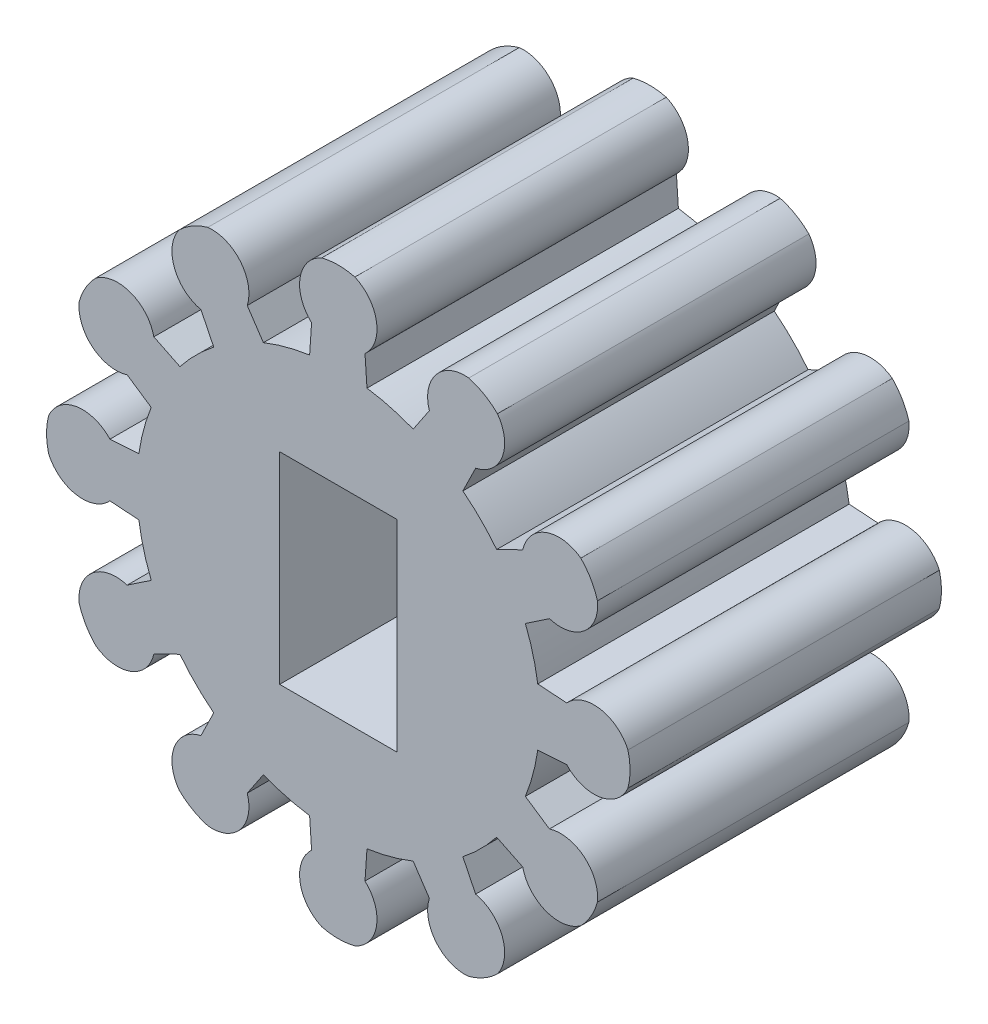
SolidWorks part; units mm, degrees
ref_plane "Front Plane" through (0, 0, 0) normal (0, 0, 1) x (1, 0, 0)
ref_plane "Top Plane" through (0, 0, 0) normal (0, 1, 0) x (1, 0, 0)
ref_plane "Right Plane" through (0, 0, 0) normal (1, 0, 0) x (0, 0, -1)
ref_plane "Plane1" through (0, 0, 20) normal (0, 0, 1) x (1, 0, 0)
ref_plane "Plane2" through (0, 0, 28.5) normal (0, 0, 1) x (1, 0, 0)
sketch "Sketch1" plane through (0, 0, 20) normal (0, 0, 1) x (1, 0, 0)
  circle A1 centre (0, 20.9252) radius 5.5
  dimension "D1" = 11
sketch "Sketch3" plane through (0, 0, 28.5) normal (0, 0, 1) x (1, 0, 0)
  line L0 (-3.9726, 20.9252) -> (15.3734, 20.9252) construction
  line L1 (0, 24.8978) -> (0, 8.7425) construction
  line L3 (-1.6, 23.6752) -> (1.6, 23.6752)
  line L4 (-1.6, 23.6752) -> (-1.6, 18.1752)
  line L5 (-1.6, 18.1752) -> (1.6, 18.1752)
  line L6 (1.6, 23.6752) -> (1.6, 18.1752)
  dimension "D1" = 3.2
  dimension "D2" = 5.5
  dimension "D3" = 1.6
  dimension "D4" = 2.75
extrude "Boss-Extrude2" add sketch "Sketch1" along normal blind 8.5
extrude "Cut-Extrude1" cut sketch "Sketch3" against normal blind 6
sketch "Sketch4" plane through (0, 0, 20) normal (0, 0, 1) x (1, 0, 0)
  line L0 (-0.729, 27.1591) -> (-0.7828, 26.3692)
  line L1 (0, 28.8881) -> (0, 27.9031) construction
  line L2 (0.729, 27.1591) -> (0.7828, 26.3692)
  line L3 (3.7483, 25.9594) -> (3.4, 25.2485)
  line L4 (2.4856, 26.6885) -> (2.044, 26.0313)
  line L5 (5.7632, 23.4108) -> (5.1061, 22.9693)
  line L6 (5.0342, 24.6735) -> (4.3232, 24.3252)
  line L7 (6.2339, 20.1962) -> (5.444, 20.1424)
  line L8 (6.2339, 21.6542) -> (5.444, 21.7081)
  line L9 (5.0342, 17.177) -> (4.3232, 17.5253)
  line L10 (5.7632, 18.4396) -> (5.1061, 18.8812)
  line L11 (2.4856, 15.162) -> (2.044, 15.8192)
  line L12 (3.7483, 15.891) -> (3.4, 16.602)
  line L13 (-0.729, 14.6913) -> (-0.7828, 15.4812)
  line L14 (0.729, 14.6913) -> (0.7828, 15.4812)
  line L15 (-3.7483, 15.891) -> (-3.4, 16.602)
  line L16 (-2.4856, 15.162) -> (-2.044, 15.8192)
  line L17 (-5.7632, 18.4396) -> (-5.1061, 18.8812)
  line L18 (-5.0342, 17.177) -> (-4.3232, 17.5253)
  line L19 (-6.2339, 21.6542) -> (-5.444, 21.7081)
  line L20 (-6.2339, 20.1962) -> (-5.444, 20.1424)
  line L21 (-5.0342, 24.6735) -> (-4.3232, 24.3252)
  line L22 (-5.7632, 23.4108) -> (-5.1061, 22.9693)
  line L23 (-2.4856, 26.6885) -> (-2.044, 26.0313)
  line L24 (-3.7483, 25.9594) -> (-3.4, 25.2485)
  circle A0 centre (0, 20.9252) radius 5.5 construction
  arc A1 (-0.729, 27.1591) -> (-0.4523, 28.8311) centre (-0.0445, 27.9047) cw
  arc A2 (-0.4523, 28.8311) -> (0.4523, 28.8311) centre (0, 27.0672) cw
  arc A3 (0.729, 27.1591) -> (0.4523, 28.8311) centre (0.0445, 27.9047) ccw
  arc A4 (-0.7828, 26.3692) -> (0.7828, 26.3692) centre (0, 20.9252) cw
  arc A5 (2.044, 26.0313) -> (3.4, 25.2485) centre (0, 20.9252) cw
  arc A6 (3.7483, 25.9594) -> (4.3446, 27.5457) centre (3.5283, 26.9474) ccw
  arc A7 (3.5612, 27.998) -> (4.3446, 27.5457) centre (3.071, 26.2443) cw
  arc A8 (2.4856, 26.6885) -> (3.5612, 27.998) centre (3.4512, 26.9919) cw
  arc A9 (4.3232, 24.3252) -> (5.1061, 22.9693) centre (0, 20.9252) cw
  arc A10 (5.7632, 23.4108) -> (7.0728, 24.4865) centre (6.0667, 24.3764) ccw
  arc A11 (6.6205, 25.2699) -> (7.0728, 24.4865) centre (5.3191, 23.9962) cw
  arc A12 (5.0342, 24.6735) -> (6.6205, 25.2699) centre (6.0221, 24.4535) cw
  arc A13 (5.444, 21.7081) -> (5.444, 20.1424) centre (0, 20.9252) cw
  arc A14 (6.2339, 20.1962) -> (7.9058, 20.4729) centre (6.9795, 20.8807) ccw
  arc A15 (7.9058, 21.3775) -> (7.9058, 20.4729) centre (6.1419, 20.9252) cw
  arc A16 (6.2339, 21.6542) -> (7.9058, 21.3775) centre (6.9795, 20.9698) cw
  arc A17 (5.1061, 18.8812) -> (4.3232, 17.5253) centre (0, 20.9252) cw
  arc A18 (5.0342, 17.177) -> (6.6205, 16.5806) centre (6.0221, 17.3969) ccw
  arc A19 (7.0728, 17.364) -> (6.6205, 16.5806) centre (5.3191, 17.8543) cw
  arc A20 (5.7632, 18.4396) -> (7.0728, 17.364) centre (6.0667, 17.4741) cw
  arc A21 (3.4, 16.602) -> (2.044, 15.8192) centre (0, 20.9252) cw
  arc A22 (2.4856, 15.162) -> (3.5612, 13.8524) centre (3.4512, 14.8586) ccw
  arc A23 (4.3446, 14.3047) -> (3.5612, 13.8524) centre (3.071, 15.6062) cw
  arc A24 (3.7483, 15.891) -> (4.3446, 14.3047) centre (3.5283, 14.9031) cw
  arc A25 (0.7828, 15.4812) -> (-0.7828, 15.4812) centre (0, 20.9252) cw
  arc A26 (-0.729, 14.6913) -> (-0.4523, 13.0194) centre (-0.0445, 13.9458) ccw
  arc A27 (0.4523, 13.0194) -> (-0.4523, 13.0194) centre (0, 14.7833) cw
  arc A28 (0.729, 14.6913) -> (0.4523, 13.0194) centre (0.0445, 13.9458) cw
  arc A29 (-2.044, 15.8192) -> (-3.4, 16.602) centre (0, 20.9252) cw
  arc A30 (-3.7483, 15.891) -> (-4.3446, 14.3047) centre (-3.5283, 14.9031) ccw
  arc A31 (-3.5612, 13.8524) -> (-4.3446, 14.3047) centre (-3.071, 15.6062) cw
  arc A32 (-2.4856, 15.162) -> (-3.5612, 13.8524) centre (-3.4512, 14.8586) cw
  arc A33 (-4.3232, 17.5253) -> (-5.1061, 18.8812) centre (0, 20.9252) cw
  arc A34 (-5.7632, 18.4396) -> (-7.0728, 17.364) centre (-6.0667, 17.4741) ccw
  arc A35 (-6.6205, 16.5806) -> (-7.0728, 17.364) centre (-5.3191, 17.8543) cw
  arc A36 (-5.0342, 17.177) -> (-6.6205, 16.5806) centre (-6.0221, 17.3969) cw
  arc A37 (-5.444, 20.1424) -> (-5.444, 21.7081) centre (0, 20.9252) cw
  arc A38 (-6.2339, 21.6542) -> (-7.9058, 21.3775) centre (-6.9795, 20.9698) ccw
  arc A39 (-7.9058, 20.4729) -> (-7.9058, 21.3775) centre (-6.1419, 20.9252) cw
  arc A40 (-6.2339, 20.1962) -> (-7.9058, 20.4729) centre (-6.9795, 20.8807) cw
  arc A41 (-5.1061, 22.9693) -> (-4.3232, 24.3252) centre (0, 20.9252) cw
  arc A42 (-5.0342, 24.6735) -> (-6.6205, 25.2699) centre (-6.0221, 24.4535) ccw
  arc A43 (-7.0728, 24.4865) -> (-6.6205, 25.2699) centre (-5.3191, 23.9962) cw
  arc A44 (-5.7632, 23.4108) -> (-7.0728, 24.4865) centre (-6.0667, 24.3764) cw
  arc A45 (-3.4, 25.2485) -> (-2.044, 26.0313) centre (0, 20.9252) cw
  arc A46 (-2.4856, 26.6885) -> (-3.5612, 27.998) centre (-3.4512, 26.9919) ccw
  arc A47 (-4.3446, 27.5457) -> (-3.5612, 27.998) centre (-3.071, 26.2443) cw
  arc A48 (-3.7483, 25.9594) -> (-4.3446, 27.5457) centre (-3.5283, 26.9474) cw
  point P97 (0, 20.9252)
  dimension "D1" = 12
extrude "Boss-Extrude3" add sketch "Sketch4" along normal up to surface (8.5 mm away) up to face at (0, 20.9252, 28.5)
